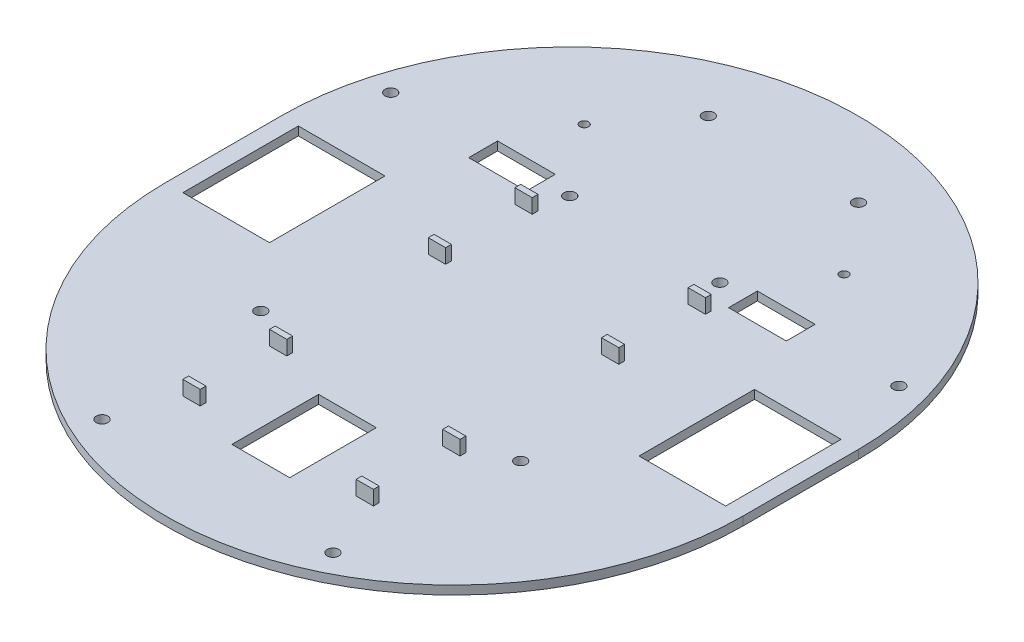
SolidWorks part; units mm, degrees
ref_plane "前视基准面" through (0, 0, 0) normal (0, 0, 1) x (1, 0, 0)
ref_plane "上视基准面" through (0, 0, 0) normal (0, 1, 0) x (1, 0, 0)
ref_plane "右视基准面" through (0, 0, 0) normal (1, 0, 0) x (0, 0, -1)
sketch "草图1" plane through (0, 0, 0) normal (0, 1, 0) x (1, 0, 0)
  line L1 (100, 0) -> (-100, 0)
  line L2 (100, 0) -> (100, 40)
  line L3 (100, 40) -> (-100, 40)
  line L4 (-100, 0) -> (-100, 40)
  circle A0 centre (0, 0) radius 100
  circle A1 centre (0, 40) radius 100
  dimension "D1" = 200
  dimension "D2" = 40
extrude "基础板" add sketch "草图1" along normal blind 3 contours L4 L3 L2 L1 | A0 | A1
sketch "草图3" plane through (0, 3, 0) normal (0, 1, 0) x (1, 0, 0)
  line L0 (0, 13.3527) -> (0, 34.0531)
  line L1 (-94, 40) -> (-64, 40)
  line L2 (-94, 40) -> (-94, 0)
  line L3 (-94, 0) -> (-64, 0)
  line L4 (-64, 40) -> (-64, 0)
  line L5 (64, 40) -> (64, 0)
  line L6 (94, 0) -> (64, 0)
  line L7 (94, 40) -> (94, 0)
  line L8 (94, 40) -> (64, 40)
  line L9 (-100, 0) -> (-100, 40) construction
  line L10 (35, 70) -> (35, 60)
  line L11 (-10, -67) -> (10, -67)
  line L12 (-10, -67) -> (-10, -37)
  line L13 (-10, -37) -> (10, -37)
  line L14 (10, -67) -> (10, -37)
  line L15 (-10, -67) -> (10, -37) construction
  line L16 (-10, -37) -> (10, -67) construction
  line L17 (-55, 70) -> (-35, 70)
  line L18 (-55, 70) -> (-55, 60)
  line L19 (-55, 60) -> (-35, 60)
  line L20 (-35, 70) -> (-35, 60)
  line L21 (55, 60) -> (35, 60)
  line L22 (55, 70) -> (55, 60)
  line L23 (55, 70) -> (35, 70)
  point P13 (0, -52)
  dimension "D1" = 6
  dimension "D2" = 30
  dimension "D3" = 52
  dimension "D4" = 30
  dimension "D5" = 20
  dimension "D6" = 60
  dimension "D7" = 35
  dimension "D8" = 20
  dimension "D9" = 10
extrude "过孔" cut sketch "草图3" against normal blind 3 contours L4 L1 L2 L3 | L7 L8 L5 L6 | L11 L14 L13 L12 | L20 L17 L18 L19 | L22 L23 L10 L21 region at (-79, 3, -20) region at (79, 3, -20) region at (45, 3, -65) region at (0, 3, 52) region at (-45, 3, -65)
sketch "草图2" plane through (0, 3, 0) normal (0, 1, 0) x (1, 0, 0)
  line L0 (0, -7.8134) -> (0, -32.4764)
  circle A0 centre (-45, -22) radius 2
  circle A1 centre (-40, -82) radius 2
  circle A2 centre (-88, 66) radius 2
  circle A3 centre (-26, 66) radius 2
  circle A4 centre (-26, 114) radius 2
  circle A5 centre (40, -82) radius 2
  circle A6 centre (45, -22) radius 2
  circle A7 centre (26, 114) radius 2
  circle A8 centre (26, 66) radius 2
  circle A9 centre (88, 66) radius 2
  circle A10 centre (-45, 90) radius 1.5
  circle A11 centre (45, 90) radius 1.5
  dimension "D1" = 4
  dimension "D2" = 4
  dimension "D3" = 4
  dimension "D4" = 4
  dimension "D5" = 4
  dimension "D6" = 45
  dimension "D7" = 22
  dimension "D8" = 40
  dimension "D9" = 82
  dimension "D10" = 26
  dimension "D11" = 88
  dimension "D12" = 26
  dimension "D13" = 66
  dimension "D14" = 66
  dimension "D15" = 114
  dimension "D16" = 3
  dimension "D17" = 90
  dimension "D18" = 45
extrude "螺丝孔" cut sketch "草图2" against normal through all contours A2 | A3 | A4 | A7 | A8 | A9 | A0 | A6 | A1 | A5 | A10 | A11 region at (-45, 3, 22) region at (-40, 3, 82) region at (-88, 3, -66) region at (-26, 3, -66) region at (-26, 3, -114) region at (40, 3, 82) region at (45, 3, 22) region at (26, 3, -114) region at (26, 3, -66) region at (88, 3, -66) region at (-45, 3, -90) region at (45, 3, -90)
sketch "草图6" plane through (0, 3, 0) normal (0, 1, 0) x (1, 0, 0)
  line L0 (0, -21.4979) -> (0, -29.8491)
  line L1 (33, -61) -> (27, -59) construction
  line L2 (-33, -29) -> (-27, -29)
  line L3 (-33, -29) -> (-33, -31)
  line L4 (-33, -31) -> (-27, -31)
  line L5 (-27, -29) -> (-27, -31)
  line L6 (-33, -29) -> (-27, -31) construction
  line L7 (-33, -31) -> (-27, -29) construction
  line L8 (-33, -59) -> (-27, -59)
  line L9 (-33, -59) -> (-33, -61)
  line L10 (-33, -61) -> (-27, -61)
  line L11 (-27, -59) -> (-27, -61)
  line L12 (-33, -59) -> (-27, -61) construction
  line L13 (-33, -61) -> (-27, -59) construction
  line L14 (-33, 26) -> (-27, 26)
  line L15 (-33, 26) -> (-33, 24)
  line L16 (-33, 24) -> (-27, 24)
  line L17 (-27, 26) -> (-27, 24)
  line L18 (-33, 26) -> (-27, 24) construction
  line L19 (-33, 24) -> (-27, 26) construction
  line L20 (-33, 56) -> (-27, 56)
  line L21 (-33, 56) -> (-33, 54)
  line L22 (-33, 54) -> (-27, 54)
  line L23 (-27, 56) -> (-27, 54)
  line L24 (-33, 56) -> (-27, 54) construction
  line L25 (-33, 54) -> (-27, 56) construction
  line L26 (33, -59) -> (27, -61) construction
  line L27 (27, -59) -> (27, -61)
  line L28 (33, -61) -> (27, -61)
  line L29 (33, -59) -> (33, -61)
  line L30 (33, -59) -> (27, -59)
  line L31 (33, -31) -> (27, -29) construction
  line L32 (33, -29) -> (27, -31) construction
  line L33 (27, -29) -> (27, -31)
  line L34 (33, -31) -> (27, -31)
  line L35 (33, -29) -> (33, -31)
  line L36 (33, -29) -> (27, -29)
  line L37 (33, 54) -> (27, 56) construction
  line L38 (33, 56) -> (27, 54) construction
  line L39 (27, 56) -> (27, 54)
  line L40 (33, 54) -> (27, 54)
  line L41 (33, 56) -> (33, 54)
  line L42 (33, 56) -> (27, 56)
  line L43 (33, 24) -> (27, 26) construction
  line L44 (33, 26) -> (27, 24) construction
  line L45 (27, 26) -> (27, 24)
  line L46 (33, 24) -> (27, 24)
  line L47 (33, 26) -> (33, 24)
  line L48 (33, 26) -> (27, 26)
  point P3 (-30, -30)
  point P8 (-30, -60)
  point P13 (-30, 25)
  point P18 (-30, 55)
  point P30 (30, -60)
  point P35 (30, -30)
  point P40 (30, 55)
  point P45 (30, 25)
  dimension "D1" = 30
  dimension "D2" = 30
  dimension "D3" = 6
  dimension "D4" = 2
  dimension "D5" = 60
  dimension "D6" = 30
  dimension "D7" = 6
  dimension "D8" = 2
  dimension "D9" = 6
  dimension "D10" = 2
  dimension "D11" = 6
  dimension "D12" = 2
  dimension "D13" = 30
  dimension "D14" = 30
  dimension "D15" = 25
  dimension "D16" = 55
extrude "固定卡槽" add sketch "草图6" along normal blind 5 contours L20 L23 L22 L21 | L14 L17 L16 L15 | L42 L39 L40 L41 | L48 L45 L46 L47 | L2 L5 L4 L3 | L8 L11 L10 L9 | L36 L33 L34 L35 | L30 L27 L28 L29
